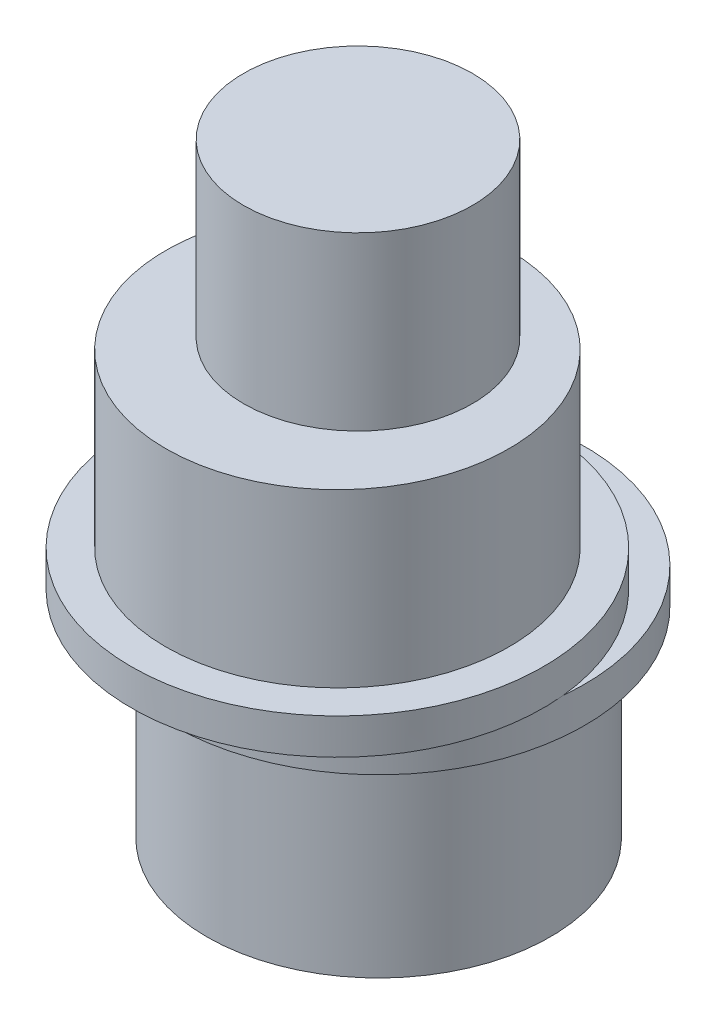
SolidWorks part; units mm, degrees
ref_plane "Front Plane" through (0, 0, 0) normal (0, 0, 1) x (1, 0, 0)
ref_plane "Top Plane" through (0, 0, 0) normal (0, 1, 0) x (1, 0, 0)
ref_plane "Right Plane" through (0, 0, 0) normal (1, 0, 0) x (0, 0, -1)
sketch "Sketch1" plane through (0, 0, 0) normal (0, 1, 0) x (1, 0, 0)
  circle A0 centre (0, 0.72) radius 6
  dimension "D1" = 12
  dimension "D2" = 0.72
extrude "Boss-Extrude1" add sketch "Sketch1" along normal blind 7
sketch "Sketch2" plane through (0, 7, 0) normal (0, 1, 0) x (1, 0, 0)
  circle A0 centre (0, 0.72) radius 7.2
  dimension "D1" = 14.4
extrude "Boss-Extrude2" add sketch "Sketch2" along normal blind 1.25
sketch "Sketch3" plane through (0, 8.25, 0) normal (0, 1, 0) x (1, 0, 0)
  circle A0 centre (0, -0.72) radius 7.2
  dimension "D1" = 14.4
  dimension "D2" = 0.72
extrude "Boss-Extrude3" add sketch "Sketch3" along normal blind 1.25
sketch "Sketch4" plane through (0, 9.5, 0) normal (0, 1, 0) x (1, 0, 0)
  circle A0 centre (0, -0.72) radius 6
  dimension "D1" = 12
  dimension "D2" = 0.72
extrude "Boss-Extrude4" add sketch "Sketch4" along normal blind 6
sketch "Sketch5" plane through (0, 0, 0) normal (0, -1, 0) x (1, 0, 0)
  line L0 (0, 0) -> (0, 2.15) construction
  line L1 (1.506, 2.15) -> (-1.506, 2.15)
  arc A0 (-1.506, 2.15) -> (1.506, 2.15) centre (0, 0) ccw
  point P7 (0, 2.15)
  dimension "D1" = 5.25
  dimension "D2" = 2.15
extrude "Cut-Extrude2" cut sketch "Sketch5" against normal blind 11 and the other way through all
sketch "Sketch6" plane through (0, 15.5, 0) normal (0, 1, 0) x (1, 0, 0)
  circle A0 centre (0, 0) radius 4
  dimension "D1" = 8
extrude "Boss-Extrude5" add sketch "Sketch6" along normal blind 6
sketch "Sketch7" plane through (0, 15.5, 0) normal (0, 1, 0) x (1, 0, 0)
  line L0 (0, 5.28) -> (0, -6.72) construction
  circle A0 centre (0, -0.72) radius 6 construction
  circle A1 centre (0, -0.72) radius 6 construction
